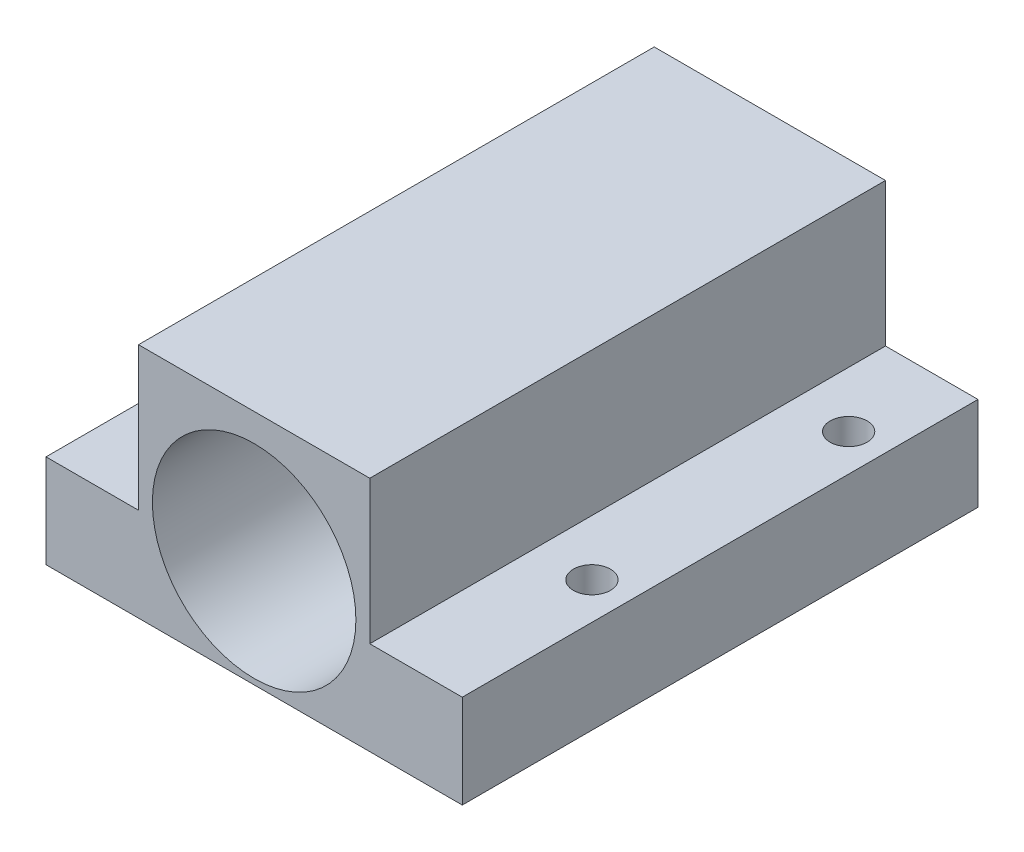
SolidWorks part; units mm, degrees
material "ABS"
ref_plane "Front Plane" through (0, 0, 0) normal (0, 0, 1) x (1, 0, 0)
ref_plane "Top Plane" through (0, 0, 0) normal (0, 1, 0) x (1, 0, 0)
ref_plane "Right Plane" through (0, 0, 0) normal (1, 0, 0) x (0, 0, -1)
sketch "Sketch1" plane through (0, 0, 0) normal (0, 0, 1) x (1, 0, 0)
  line L0 (-65.4098, -16.7) -> (184.5902, -16.7) construction
  line L1 (-13.5149, 8.9) -> (11.4851, 8.9)
  line L2 (-13.5149, 8.9) -> (-13.5149, -16.7)
  line L3 (-13.5149, -16.7) -> (11.4851, -16.7)
  line L4 (11.4851, 8.9) -> (11.4851, -16.7)
  line L5 (-13.5149, 8.9) -> (11.4851, -16.7) construction
  line L6 (-13.5149, -16.7) -> (11.4851, 8.9) construction
  line L7 (11.4851, -16.7) -> (21.4851, -16.7)
  line L8 (11.4851, -16.7) -> (11.4851, -6.6)
  line L9 (11.4851, -6.6) -> (21.4851, -6.6)
  line L10 (21.4851, -16.7) -> (21.4851, -6.6)
  line L11 (11.4851, -16.7) -> (21.4851, -6.6) construction
  line L12 (11.4851, -6.6) -> (21.4851, -16.7) construction
  line L13 (-13.5149, -16.7) -> (-23.5149, -16.7)
  line L14 (-13.5149, -16.7) -> (-13.5149, -6.6)
  line L15 (-13.5149, -6.6) -> (-23.5149, -6.6)
  line L16 (-23.5149, -16.7) -> (-23.5149, -6.6)
  line L17 (-13.5149, -16.7) -> (-23.5149, -6.6) construction
  line L18 (-13.5149, -6.6) -> (-23.5149, -16.7) construction
  circle A0 centre (-1.0149, -5.1) radius 4.1
  circle A1 centre (-1.0149, -5.1) radius 11
  point P8 (0, -5.2)
  point P14 (16.4851, -11.65)
  point P16 (-18.5149, -11.65)
  dimension "D4" = 8.2
  dimension "D5" = 22
  dimension "D11" = 14
  dimension "D2" = 0
  dimension "D3" = 25
  dimension "D6" = 10
  dimension "D8" = 10
  dimension "D9" = 10.1
  dimension "D10" = 12.5
  dimension "D12" = 11.6
  dimension "D13" = 5.2
extrude "Boss-Extrude1" add sketch "Sketch1" along normal up to surface (55.75 mm away) contours L4 L1 L2 L3 A1 | L16 L13 L2 L15 | L7 L10 L9 L4 region at (-1.0149, 8.5422, 0) region at (-18.5149, -11.65, 0) region at (16.4851, -11.65, 0)
sketch "Sketch2" plane through (0, -6.6, 0) normal (0, 1, 0) x (1, 0, 0)
  line L0 (-23.5149, 0) -> (-13.5149, -55.75)
  line L1 (-13.5149, -55.75) -> (-23.5149, -55.75)
  line L2 (-23.5149, -55.75) -> (-13.5149, 0)
  line L3 (11.4851, 0) -> (21.4851, -55.75)
  line L4 (21.4851, -55.75) -> (21.4851, 0)
  line L5 (21.4851, 0) -> (11.4851, -55.75)
  circle A0 centre (-17.5, -10) radius 2
  circle A1 centre (17.5, -10) radius 2
  circle A2 centre (17.5, -10) radius 2 construction
  circle A3 centre (-17.5, -10) radius 2 construction
  circle A4 centre (-17.5, -37.75) radius 2
  circle A5 centre (17.5, -37.75) radius 2
  circle A6 centre (17.5, -37.75) radius 2 construction
  circle A7 centre (-17.5, -37.75) radius 2 construction
  dimension "D1" = 4
  dimension "D2" = 4
extrude "Cut-Extrude1" cut sketch "Sketch2" against normal through all contours A0 | A4 | A1 | A5
